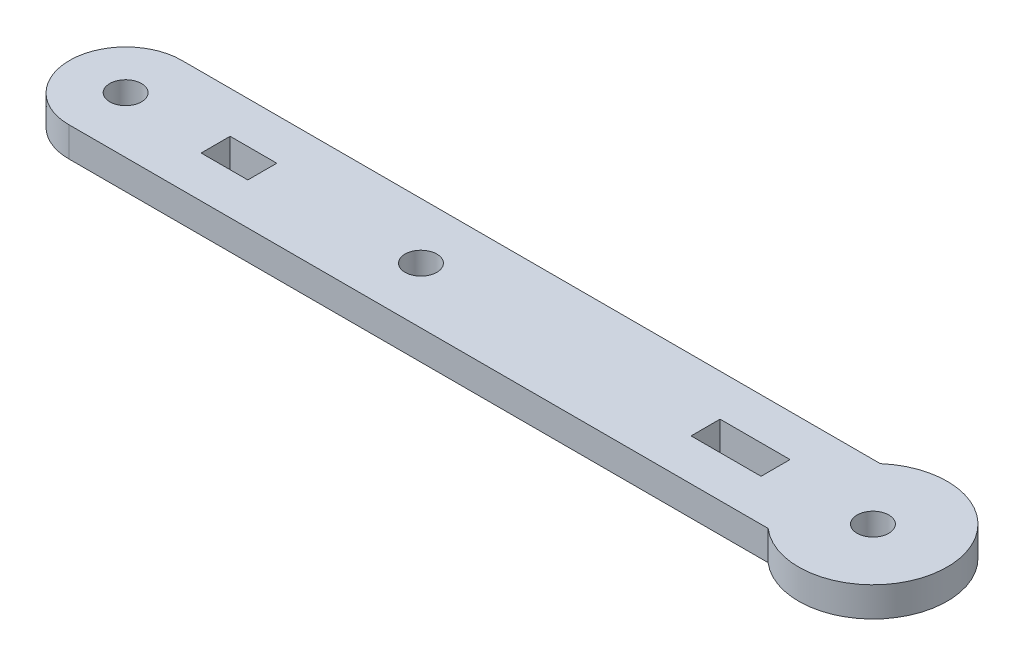
SolidWorks part; units mm, degrees
material "Acrylic (Medium-high impact)"
ref_plane "Front Plane" through (0, 0, 0) normal (0, 0, 1) x (1, 0, 0)
ref_plane "Top Plane" through (0, 0, 0) normal (0, 1, 0) x (1, 0, 0)
ref_plane "Right Plane" through (0, 0, 0) normal (1, 0, 0) x (0, 0, -1)
sketch "Sketch1" plane through (0, 0, 0) normal (0, 1, 0) x (1, 0, 0)
  line L2 (-1.7189, 1.1496) -> (-76.5203, 1.1501)
  line L3 (-76.4412, 13.1501) -> (-1.7189, 13.1501)
  line L5 (-66.8144, 8.6499) -> (-66.8144, 8.6999)
  line L6 (-66.8144, 8.6999) -> (-61.8232, 8.6999)
  line L7 (-61.8232, 8.6999) -> (-61.8232, 8.6499)
  line L8 (-61.8232, 8.6499) -> (-61.8232, 5.6497)
  line L9 (-61.8232, 5.6497) -> (-61.8232, 5.5999)
  line L10 (-61.8232, 5.5999) -> (-66.8144, 5.5999)
  line L11 (-66.8144, 5.5999) -> (-66.8144, 5.6497)
  line L12 (-66.8144, 5.6497) -> (-66.8144, 8.6499)
  line L13 (-14.4073, 8.6999) -> (-6.9206, 8.6999)
  line L14 (-6.9206, 8.6999) -> (-6.9206, 5.5999)
  line L15 (-6.9206, 5.5999) -> (-14.4073, 5.5999)
  line L16 (-14.4073, 5.5999) -> (-14.4073, 8.6999)
  circle A0 centre (3.4934, 7.1498) radius 1.7
  arc A1 (-1.7189, 13.1501) -> (-1.7189, 1.1496) centre (3.4934, 7.1498) cw
  circle A2 centre (-44.8535, 7.1498) radius 1.7
  circle A3 centre (-76.4412, 7.1498) radius 1.7
  spline S2 degree 3 poles (-76.5203, 1.1501) (-79.8281, 1.1501) (-82.4305, 3.836) (-82.4305, 7.1498) knots 2 2 2 2 3 3 3 3
  spline S3 degree 3 poles (-82.4305, 7.1498) (-82.4305, 10.4636) (-79.749, 13.1501) (-76.4412, 13.1501) knots 3 3 3 3 4 4 4 4
  point P5 (0, 0)
  point P12 (0, 0)
  point P13 (-61.8232, 7.1498)
  point P14 (-14.4073, 7.1499)
  point P15 (-6.9206, 7.1499)
  dimension "D1" = 3.4
  dimension "D5" = 30.4462
  dimension "D2" = 7.4867
  dimension "D3" = 4.9912
  dimension "D4" = 16.9697
  dimension "D6" = 10.414
extrude "Boss-Extrude1" add sketch "Sketch1" along normal blind 3.175
